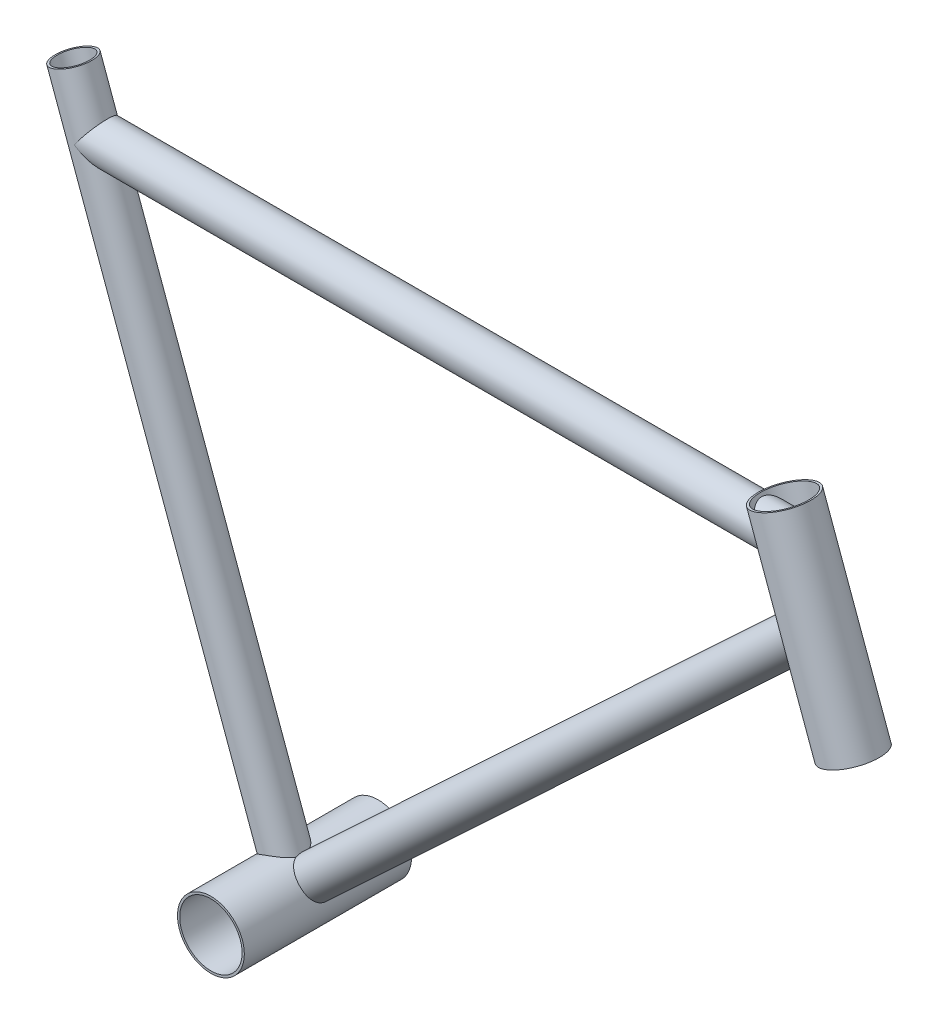
SolidWorks part; units mm, degrees
ref_plane "Alzado" through (0, 0, 0) normal (0, 0, 1) x (1, 0, 0)
ref_plane "Planta" through (0, 0, 0) normal (0, 1, 0) x (1, 0, 0)
ref_plane "Vista lateral" through (0, 0, 0) normal (1, 0, 0) x (0, 0, -1)
sketch "Croquis1" plane through (0, 0, 0) normal (0, 0, 1) x (1, 0, 0)
  circle A0 centre (0, 0) radius 28
  circle A2 centre (0, 0) radius 30
  dimension "D1" = 60
  dimension "D2" = 2
extrude "Saliente-Extruir1" add sketch "Croquis1" along normal blind 150
sketch "Croquis2" plane through (0, 0, 0) normal (0, 0, 1) x (1, 0, 0)
  line L0 (0, -228.2812) -> (0, 372.8863) construction
  line L1 (0, 0) -> (-131.6879, 361.8097) construction
  dimension "D1" = 20
ref_plane "Plano1" through (-10.2606, 28.1908, 0) normal (-0.342, 0.9397, 0) x (0.9397, 0.342, 0)
sketch "Croquis3" plane through (-10.2606, 28.1908, 0) normal (-0.342, 0.9397, 0) x (0.9397, 0.342, 0)
  line L0 (30, -75) -> (-30, -75) construction
  line L1 (-30, 0) -> (30, 0)
  line L2 (-30, 0) -> (-30, -150)
  line L3 (-30, -150) -> (30, -150)
  line L4 (30, 0) -> (30, -150)
  line L5 (0, 0) -> (0, -150) construction
  circle A0 centre (0, -75) radius 15.5
  circle A1 centre (0, -75) radius 17.5
  dimension "D2" = 2
  dimension "D1" = 35
extrude "Saliente-Extruir2" add sketch "Croquis3" along normal blind 550 and the other way up to surface separate body contours A1 A0 region at (-26.2401, 22.3747, 75) other way up to face at (30, 0, 150)
sketch "Croquis4" plane through (0, 0, 0) normal (1, 0, 0) x (0, 0, -1)
  line L0 (0, 30) -> (-150, 30) construction
  line L1 (-57.5, 545.0217) -> (-92.5, 545.0217) construction
  line L2 (-57.5, 545.0217) -> (-57.5, 30) construction
  line L3 (-57.5, 30) -> (-92.5, 30) construction
  line L4 (-92.5, 545.0217) -> (-92.5, 30) construction
  line L5 (-92.5, 545.0217) -> (-92.5, 28.1907) construction
  line L6 (-75, 545.0217) -> (-75, 495.0217) construction
  circle A0 centre (-75, 495.0217) radius 17.5
  circle A1 centre (-75, 495.0217) radius 15.5
  dimension "D2" = 35
  dimension "D1" = 50
  dimension "D3" = 2
extrude "Saliente-Extruir3" add sketch "Croquis4" along normal blind 450 and the other way up to surface other way up to face at (-214.8163, 539.0364, 75)
sketch "Croquis5" plane through (0, 0, 0) normal (0, 0, 1) x (1, 0, 0)
  line L0 (450, 495.0217) -> (0, 495.0217) construction
  line L1 (450, 477.5217) -> (450, 512.5217) construction
  line L2 (0, -82.5) -> (0, 82.5) construction
  line L3 (450, 364.6601) -> (450, 737.8051) construction
  line L4 (450, 495.0217) -> (518.5439, 306.6988) construction
  dimension "D1" = 20
ref_plane "Plano2" through (450, 495.0217, 0) normal (0.342, -0.9397, 0) x (-0.9397, -0.342, 0)
sketch "Croquis6" plane through (450, 495.0217, 0) normal (0.342, -0.9397, 0) x (-0.9397, -0.342, 0)
  line L0 (592.1691, -57.5) -> (0, -57.5) construction
  line L1 (0, -92.5) -> (133.6203, -92.5)
  line L2 (0, -92.5) -> (0, -57.5)
  line L3 (0, -57.5) -> (133.6203, -57.5)
  line L4 (133.6203, -92.5) -> (133.6203, -57.5)
  circle A0 centre (0, -75) radius 25
  circle A1 centre (0, -75) radius 23
  dimension "D2" = 2
  dimension "D1" = 50
extrude "Saliente-Extruir5" add sketch "Croquis6" along normal blind 150 and the other way blind 30 contours A1 L1 A0 L3 | A1 L3 A0 L1 region at (430.0648, 487.7659, 84.7892) region at (434.5992, 489.4163, 93.1585)
sketch "Croquis7" plane through (0, 0, 0) normal (0, 0, 1) x (1, 0, 0)
  line L0 (0, 0) -> (450.4491, 420.6927) construction
  line L2 (429.765, 477.5218) -> (477.8107, 345.5173) construction
  line L3 (450.4491, 420.6927) -> (477.8107, 345.5173) construction
  dimension "D1" = 80
ref_plane "Plano3" through (21.925, 20.4767, 0) normal (0.7308, 0.6826, 0) x (0, 0, -1)
sketch "Croquis8" plane through (21.925, 20.4767, 0) normal (0.7308, 0.6826, 0) x (0, 0, -1)
  line L0 (-75, 30) -> (-75, -30) construction
  line L1 (-150, -30) -> (0, -30)
  line L2 (-150, -30) -> (-150, 30)
  line L3 (-150, 30) -> (0, 30)
  line L4 (0, -30) -> (0, 30)
  line L6 (0, 0) -> (-150, 0) construction
  circle A0 centre (-75, 0) radius 17.5
  circle A1 centre (-75, 0) radius 15.5
  dimension "D2" = 2
  dimension "D1" = 35
extrude "Saliente-Extruir6" add sketch "Croquis8" along normal up to surface and the other way up to surface contours A0 A1 region at (21.925, 20.4767, 92.005) up to face at (431.6933, 492.6661, 92.3407) other way up to face at (30, 0, 150)
equation "\"DiamExtEjeCentral\"=60"
equation "\"D1@Croquis1\"=\"DiamExtEjeCentral\""
equation "\"GrosorEjeCentral\"=2"
equation "\"D2@Croquis1\"=\"GrosorEjeCentral\""
equation "\"LargoEjeCentral\"=150"
equation "\"D1@Saliente-Extruir1\"=\"LargoEjeCentral\""
equation "\"AngSopAsiento\"=20"
equation "\"D1@Croquis2\"=\"AngSopAsiento\""
equation "\"GrosorGeneral\"=2"
equation "\"D2@Croquis3\"=\"GrosorGeneral\""
equation "\"LargoSoporteAsiento\"=550"
equation "\"D1@Saliente-Extruir2\"=\"LargoSoporteAsiento\""
equation "\"DistAsientoSoporteRecto\"=50"
equation "\"D1@Croquis4\"=\"DistAsientoSoporteRecto\""
equation "\"DiamExtTuboGeneral\" = 35.00mm"
equation "\"D2@Croquis4\"=\"DiamExtTuboGeneral\""
equation "\"D3@Croquis4\"=\"GrosorGeneral\""
equation "\"largoSoporteRecto\"=450"
equation "\"D1@Saliente-Extruir3\"=\"largoSoporteRecto\""
equation "\"anguloManibrio\"=20"
equation "\"D1@Croquis5\"=\"anguloManibrio\""
equation "\"DiamExtTuboManibrios\"=50"
equation "\"D1@Croquis6\"=\"DiamExtTuboManibrios\""
equation "\"D2@Croquis6\"=\"GrosorGeneral\""
equation "\"largoSupTuboManibrio\" = 30"
equation "\"D2@Saliente-Extruir5\"=\"largoSupTuboManibrio\""
equation "\"largoInfTuboManib\" = 150"
equation "\"D1@Saliente-Extruir5\"=\"largoInfTuboManib\""
equation "\"distTuboInfManibrio\"=80"
equation "\"D1@Croquis7\"=\"distTuboInfManibrio\""
equation "\"D1@Croquis8\"=\"DiamExtTuboGeneral\""
equation "\"D2@Croquis8\"=\"GrosorGeneral\""
